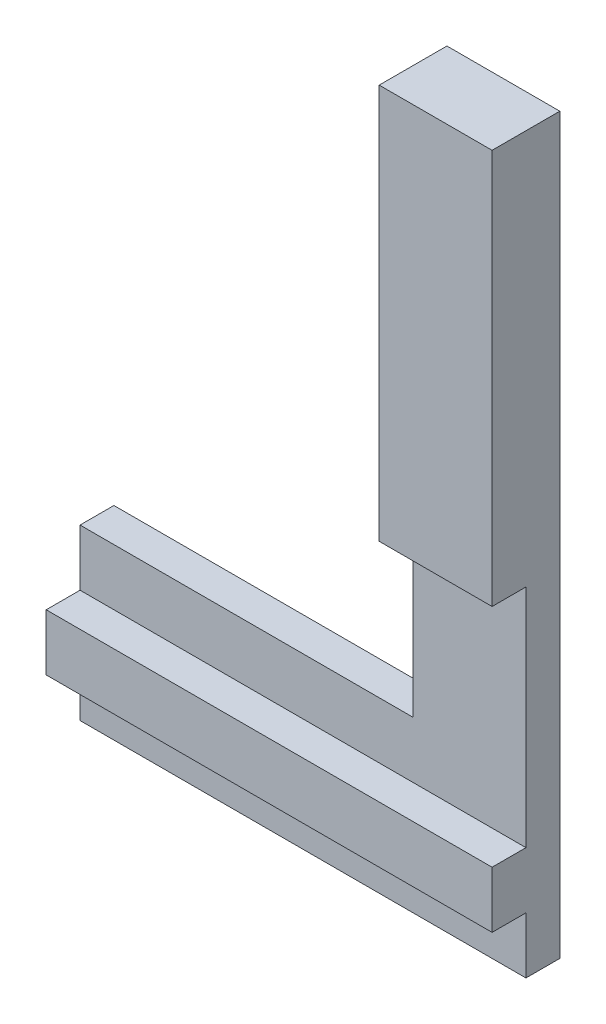
SolidWorks part; units mm, degrees
ref_plane "Front Plane" through (0, 0, 0) normal (0, 0, 1) x (1, 0, 0)
ref_plane "Top Plane" through (0, 0, 0) normal (0, 1, 0) x (1, 0, 0)
ref_plane "Right Plane" through (0, 0, 0) normal (1, 0, 0) x (0, 0, -1)
sketch "Sketch1" plane through (0, 0, 0) normal (0, 0, 1) x (1, 0, 0)
  line L3 (79, 0) -> (0, 0)
  line L4 (0, 0) -> (0, -30)
  line L5 (0, -30) -> (79, -30)
  line L6 (79, -30) -> (79, 0)
  line L9 (0, 0) -> (20, 0)
  line L26 (0, 0) -> (0, -30)
  line L28 (79, 0) -> (59, 0)
  line L29 (79, 0) -> (79, 100)
  line L30 (79, 100) -> (59, 100)
  line L31 (59, 0) -> (59, 100)
  dimension "D1" = 20
  dimension "D2" = 100
  dimension "D3" = 79
  dimension "D4" = 30
extrude "Boss-Extrude4" add sketch "Sketch1" along normal blind 6 contours L31 L3 region at (69, 50, 0)
extrude "Boss-Extrude5" add sketch "Sketch1<8>" along normal blind 6 contours L5 L6 L3 L4 region at (39.5, -15, 0)
sketch "Sketch1<8>" plane through (0, 0, 0) normal (0, 0, 1) x (1, 0, 0) same geometry as "Sketch1"
sketch "Sketch3" plane through (0, 0, 6) normal (0, 0, 1) x (1, 0, 0)
  line L1 (0, -10) -> (79, -10)
  line L2 (0, -10) -> (0, -20)
  line L3 (0, -20) -> (79, -20)
  line L4 (79, -10) -> (79, -20)
  line L5 (79, -30) -> (79, 100) construction
  point P8 (0, 0)
  dimension "D1" = 10
  dimension "D2" = 10
extrude "Boss-Extrude6" add sketch "Sketch3" along normal blind 6
sketch "Sketch6" plane through (0, 0, 6) normal (0, 0, 1) x (1, 0, 0)
  line L5 (79, -10) -> (79, 100) construction
  line L6 (59, 100) -> (79, 100)
  line L7 (59, 100) -> (59, 30)
  line L8 (59, 30) -> (79, 30)
  line L9 (79, 100) -> (79, 30)
  line M5 (59, 100) -> (59, 0)
  dimension "D1" = 70
extrude "Boss-Extrude8" add sketch "Sketch6" along normal blind 6 contours M5 region at (69, 65, 6)
